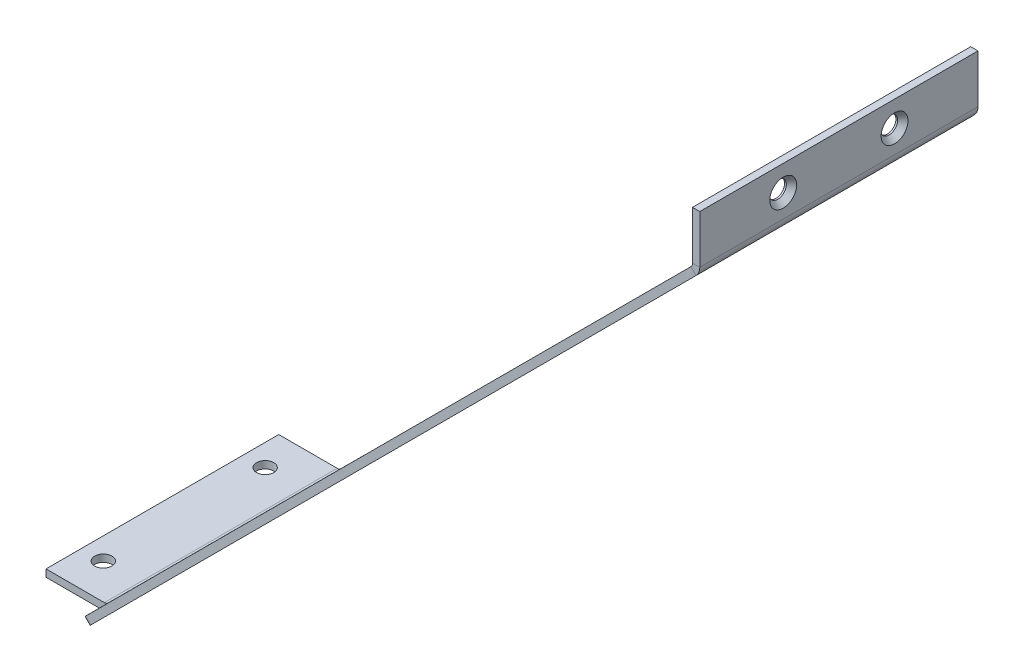
SolidWorks part; units mm, degrees
note: The reader was unsure of these and kept them because the rebuilt part matched: bend radius of "BaseBend1", "BaseBend2".
ref_plane "Front Plane" through (0, 0, 0) normal (0, 0, 1) x (1, 0, 0)
ref_plane "Top Plane" through (0, 0, 0) normal (0, 1, 0) x (1, 0, 0)
ref_plane "Right Plane" through (0, 0, 0) normal (1, 0, 0) x (0, 0, -1)
sketch "Sketch1" plane through (0, 0, 0) normal (0, 0, 1) x (1, 0, 0)
  line L0 (139.7, -25.4) -> (139.7, -41.275)
  line L1 (139.7, -41.275) -> (-51.308, -232.283)
  line L2 (-51.308, -232.283) -> (-70.358, -232.283)
  dimension "D1" = 45
  dimension "D2" = 15.875
  dimension "D3" = 19.05
  dimension "D4" = 232.283
  dimension "D5" = 139.7
  dimension "D6" = 41.275
sheet metal parameters "Sheet-Metal1" thickness 2.286 parameters "D1"=1.7272
base flange "Base-Flange1" sketch "Sketch1" end condition mid plane depth 87.3252 reverse direction no thickness 2.286 reverse thickness direction yes bend radius 1.7272
bend "BaseBend1" bend radius 1.7272 bend angle 45 parameters "D5"=1
bend "BaseBend2" bend radius 1.7272 bend angle 45 parameters "D5"=2
sketch "Sketch3" plane through (92.1039, -92.1039, 0) normal (0.7071, -0.7071, 0) x (0, 0, -1)
  line L1 (-75.8805, -259.354) -> (-36.5252, -259.354)
  line L2 (-75.8805, -259.354) -> (-75.8805, -200.025)
  line L3 (-75.8805, -200.025) -> (-36.5252, -200.025)
  line L4 (-36.5252, -259.354) -> (-36.5252, -200.025)
  line L5 (75.8805, -200.025) -> (36.5252, -200.025)
  line L6 (75.8805, -200.025) -> (75.8805, -259.354)
  line L7 (75.8805, -259.354) -> (36.5252, -259.354)
  line L8 (36.5252, -200.025) -> (36.5252, -259.354)
  dimension "D1" = 200.025
  dimension "D2" = 36.5252
  dimension "D3" = 36.5252
extrude "Cut-Extrude1" cut sketch "Sketch3" against normal through all
hole_wizard "CSK for #8 Flat Head Machine Screw1" positions "Sketch5" profile "Sketch4" countersink size "#8" standard "Ansi Inch" end condition up to next
sketch "Sketch5" plane through (141.986, 0, 0) normal (1, 0, 0) x (0, 0, -1)
  line L0 (-43.6626, -25.4) -> (43.6626, -25.4) construction
  point P0 (17.4752, -33.3502)
  point P1 (-17.4752, -33.3502)
  point P4 (0, -25.4)
  dimension "D1" = 7.9502
  dimension "D2" = 17.4752
  dimension "D3" = 17.4752
sketch "Sketch4" plane through (141.986, -33.3502, -17.4752) normal (0, 1, 0) x (0, 0, -1)
  line L0 (0, 0) -> (0, 2.286)
  line L1 (0, 2.286) -> (2.7051, 2.286)
  line L2 (2.7051, 2.286) -> (2.7051, 1.7386)
  line L3 (2.7051, 1.7386) -> (4.2164, 0)
  line L5 (4.2164, 0) -> (0, 0)
  line L6 (-2.7051, 1.7386) -> (-4.2164, 0) construction
  line L11 (0, -6.35) -> (0, 107.95) construction
  dimension "Thru Hole Dia." = 5.4102
  dimension "Thru Hole Depth" = 2.286
  dimension "Near C'Sink Dia." = 8.4328
  dimension "Near C'Sink Angle" = 82
sketch "Sketch6" plane through (92.1039, -92.1039, 0) normal (0.7071, -0.7071, 0) x (0, 0, -1)
  line L0 (0, -79.851) -> (0, -148.0368) construction
  line L1 (-43.6626, 68.8816) -> (43.6626, 68.8816) construction
  circle A0 centre (0, 56.897) radius 3.175
  circle A1 centre (25.4, 44.197) radius 2.0193
  circle A2 centre (25.4, -32.003) radius 2.0193
  circle A3 centre (25.4, -108.203) radius 2.0193
  circle A4 centre (-25.4, -108.203) radius 2.0193
  circle A5 centre (-25.4, -32.003) radius 2.0193
  circle A6 centre (-25.4, 44.197) radius 2.0193
  circle A7 centre (0, -32.003) radius 2.7051
  circle A8 centre (25.4, -184.403) radius 2.0193
  circle A9 centre (-25.4, -184.403) radius 2.0193
  circle A10 centre (0, -83.5184) radius 2.7051
  dimension "D1" = 6.35
  dimension "D3" = 76.2
  dimension "D4" = 76.2
  dimension "D5" = 50.8
  dimension "D6" = 25.4
  dimension "D7" = 4.0386
  dimension "D8" = 5.4102
  dimension "D9" = 88.9
  dimension "D10" = 76.2
  dimension "D2" = 12.7
  dimension "D11" = 152.4
extrude "Cut-Extrude2" cut sketch "Sketch6" against normal blind 7.62
sketch "Sketch7" plane through (0, -234.569, 0) normal (0, -1, 0) x (1, 0, 0)
  circle A0 centre (-63.5, 25.4) radius 2.7051
  circle A1 centre (-63.5, -25.4) radius 2.7051
  dimension "D1" = 6.858
  dimension "D2" = 25.4
  dimension "D4" = 5.4102
  dimension "D3" = 25.4
extrude "Cut-Extrude3" cut sketch "Sketch7" against normal up to next
sketch "Sketch8" plane through (92.1039, -92.1039, 0) normal (0.7071, -0.7071, 0) x (0, 0, -1)
  line L0 (64.6324, -80.2164) -> (35.7124, -80.2164)
  line L1 (35.7124, -86.8204) -> (64.6324, -86.8204)
  line L2 (64.6324, -86.8204) -> (64.6324, -80.2164)
  line L3 (-43.6626, 68.8816) -> (43.6626, 68.8816) construction
  line L4 (0, -79.851) -> (0, -148.0368) construction
  line L5 (43.6626, 68.8816) -> (43.6626, -199.8137) construction
  arc A0 (35.7124, -80.2164) -> (35.7124, -86.8204) centre (35.7124, -83.5184) ccw
  dimension "D1" = 152.4
  dimension "D2" = 6.604
  dimension "D3" = 35.7124
  dimension "D4" = 7.9502
extrude "CE-00 Notch for Wire" cut sketch "Sketch8" against normal up to next
flat pattern "Flat-Pattern1"
sketch "Bend-Lines1" plane through (92.1039, -92.1039, 0) normal (0.7071, -0.7071, 0) x (0.7071, 0.7071, 0)
  line L0 (69.9548, 43.6626) -> (69.9548, -43.6626) construction
  line L1 (-200.887, 36.5252) -> (-200.887, -36.5252) construction
  line L2 (69.9548, 43.6626) -> (69.9548, -43.6626) construction
  line L3 (-200.887, 36.5252) -> (-200.887, -36.5252) construction
bend of the flat pattern "Flatten-<BaseBend1>1"
bend of the flat pattern "Flatten-<BaseBend2>1"
sketch "Sketch9" [suppressed] plane through (92.1039, -92.1039, 0) normal (0.7071, -0.7071, 0) x (0, 0, -1)
  line L0 (-43.6626, 86.1877) -> (43.6626, 86.1877) construction
  line L1 (-43.6626, 86.1877) -> (-43.6626, -199.8137) construction
  line L2 (-36.5252, -199.9577) -> (-36.5252, -220.2948) construction
  line L3 (-43.6626, -199.9577) -> (-36.5252, -199.9577) construction
  line L4 (-36.5252, -220.2948) -> (36.5252, -220.2948) construction
  line L5 (36.5252, -220.2948) -> (36.5252, -199.9577) construction
  line L6 (36.5252, -199.9577) -> (43.6626, -199.9577) construction
  line L7 (-43.6626, 86.1877) -> (43.6626, 86.1877)
  line L8 (-43.6626, 86.1877) -> (-43.6626, -199.9577)
  line L9 (-36.5252, -199.9577) -> (-36.5252, -220.2948)
  line L10 (-43.6626, -199.9577) -> (-36.5252, -199.9577)
  line L11 (-36.5252, -220.2948) -> (36.5252, -220.2948)
  line L12 (36.5252, -220.2948) -> (36.5252, -199.9577)
  line L13 (36.5252, -199.9577) -> (43.6626, -199.9577)
  line L14 (43.6626, -199.9577) -> (43.6626, 86.1877)
sketch "Sketch10" [suppressed] plane through (92.1039, -92.1039, 0) normal (0.7071, -0.7071, 0) x (0, 0, -1)
  line L0 (36.5252, -220.2948) -> (36.5252, -199.9577) construction
  line L1 (36.5252, -199.9577) -> (43.6626, -199.9577) construction
  line L2 (-43.6626, -199.9577) -> (-36.5252, -199.9577) construction
  line L3 (-36.5252, -199.9577) -> (-36.5252, -220.2948) construction
  circle A0 centre (38.5064, -201.9389) radius 1.9812
  circle A1 centre (-38.5064, -201.9389) radius 1.9812
  dimension "D1" = 3.9624
